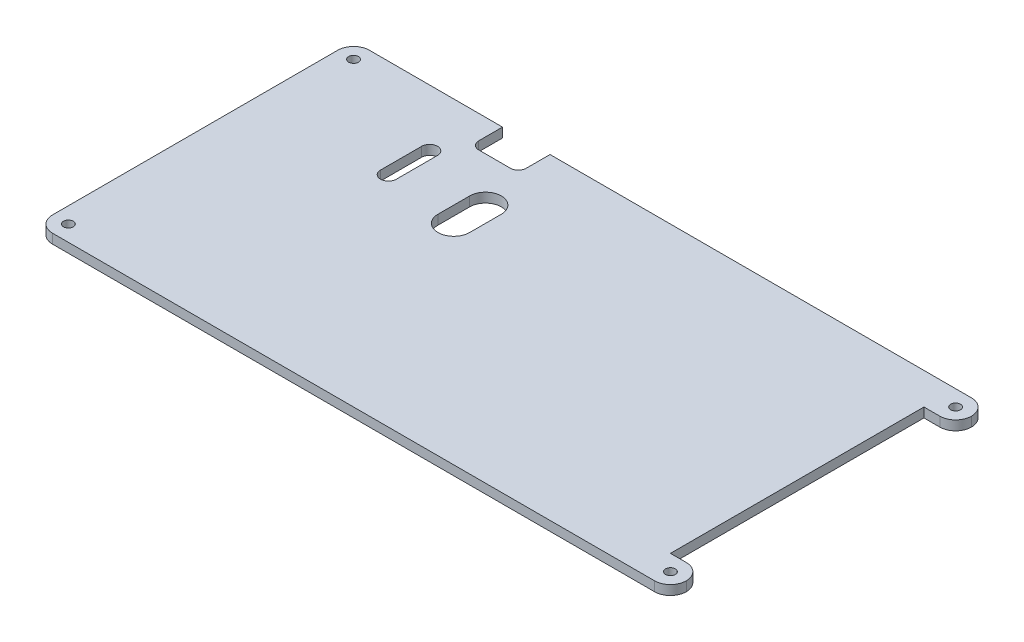
SolidWorks part; units mm, degrees
ref_plane "Front Plane" through (0, 0, 0) normal (0, 0, 1) x (1, 0, 0)
ref_plane "Top Plane" through (0, 0, 0) normal (0, 1, 0) x (1, 0, 0)
ref_plane "Right Plane" through (0, 0, 0) normal (1, 0, 0) x (0, 0, -1)
sketch "Sketch1" plane through (0, 0, 0) normal (0, 1, 0) x (1, 0, 0)
  line L1 (-100, 50) -> (100, 50)
  line L2 (-100, 50) -> (-100, -50)
  line L3 (-100, -50) -> (100, -50)
  line L4 (100, 50) -> (100, -50)
  line L5 (-100, 50) -> (100, -50) construction
  line L6 (-100, -50) -> (100, 50) construction
  point P0 (0, 0)
  dimension "D1" = 200
  dimension "D2" = 100
extrude "Boss-Extrude1" add sketch "Sketch1" along normal blind 3 contours L1 L4 L3 L2
sketch "Sketch2" plane through (0, 3, 0) normal (0, 1, 0) x (1, 0, 0)
  line L0 (-100, 50) -> (100, 50) construction
  line L1 (-100, 50) -> (-100, -50) construction
  line L2 (-100, -50) -> (100, -50) construction
  line L3 (100, 50) -> (100, -50) construction
  circle A0 centre (-95, 45) radius 1.55
  circle A1 centre (-95, -45) radius 1.55
  circle A2 centre (95, 45) radius 1.55
  circle A3 centre (95, -45) radius 1.55
  dimension "D3" = 3.1
  dimension "D4" = 3.1
  dimension "D5" = 3.1
  dimension "D6" = 3.1
  dimension "D1" = 5
  dimension "D2" = 5
  dimension "D7" = 5
  dimension "D8" = 5
  dimension "D9" = 5
  dimension "D10" = 5
  dimension "D11" = 5
  dimension "D12" = 5
extrude "Cut-Extrude1" cut sketch "Sketch2" against normal through all
fillet "Fillet1" radius 5 4 edges at (-100, 1.5, -50) (100, 1.5, -50) (100, 1.5, 50) (-100, 1.5, 50)
sketch "Sketch3" plane through (0, 3, 0) normal (0, 1, 0) x (1, 0, 0)
  line L0 (100, 45) -> (100, -45) construction
  line L1 (100, 40) -> (90, 40)
  line L2 (100, 40) -> (100, -40)
  line L3 (100, -40) -> (90, -40)
  line L4 (90, 40) -> (90, -40)
  line L5 (-95, 50) -> (95, 50) construction
  line L6 (-95, -50) -> (95, -50) construction
  line L12 (-58, 32) -> (-58, 19) construction
  line L13 (-55.5, 32) -> (-55.5, 19)
  line L18 (-34.365, 26) -> (-34.365, 16) construction
  line L19 (-29.365, 26) -> (-29.365, 16)
  line L20 (-60.5, 32) -> (-60.5, 19)
  line L21 (-100, 45) -> (-100, -45) construction
  line L22 (-39.365, 26) -> (-39.365, 16)
  line L23 (-53, 40) -> (-38, 40)
  line L24 (-53, 40) -> (-53, 50)
  line L25 (-53, 50) -> (-38, 50)
  line L26 (-38, 40) -> (-38, 50)
  line L27 (-53, 40) -> (-38, 50) construction
  line L28 (-53, 50) -> (-38, 40) construction
  arc A2 (-55.5, 32) -> (-60.5, 32) centre (-58, 32) ccw
  arc A3 (-60.5, 19) -> (-55.5, 19) centre (-58, 19) ccw
  arc A4 (-29.365, 26) -> (-39.365, 26) centre (-34.365, 26) ccw
  arc A5 (-39.365, 16) -> (-29.365, 16) centre (-34.365, 16) ccw
  point P12 (-58, 25.5)
  point P17 (-34.365, 21)
  point P26 (-45.5, 45)
  dimension "D1" = 10
  dimension "D2" = 10
  dimension "D3" = 10
  dimension "D4" = 42
  dimension "D5" = 75.5
  dimension "D6" = 5
  dimension "D7" = 13
  dimension "D8" = 65.635
  dimension "D9" = 71
  dimension "D10" = 10
  dimension "D11" = 10
  dimension "D12" = 10
  dimension "D13" = 54.5
  dimension "D14" = 15
extrude "Cut-Extrude2" cut sketch "Sketch3" against normal through all
fillet "Fillet2" radius 5 2 edges at (100, 1.5, 40) (100, 1.5, -40)
fillet "Fillet4" radius 2.5 2 edges at (-38, 1.5, -40) (-53, 1.5, -40)
